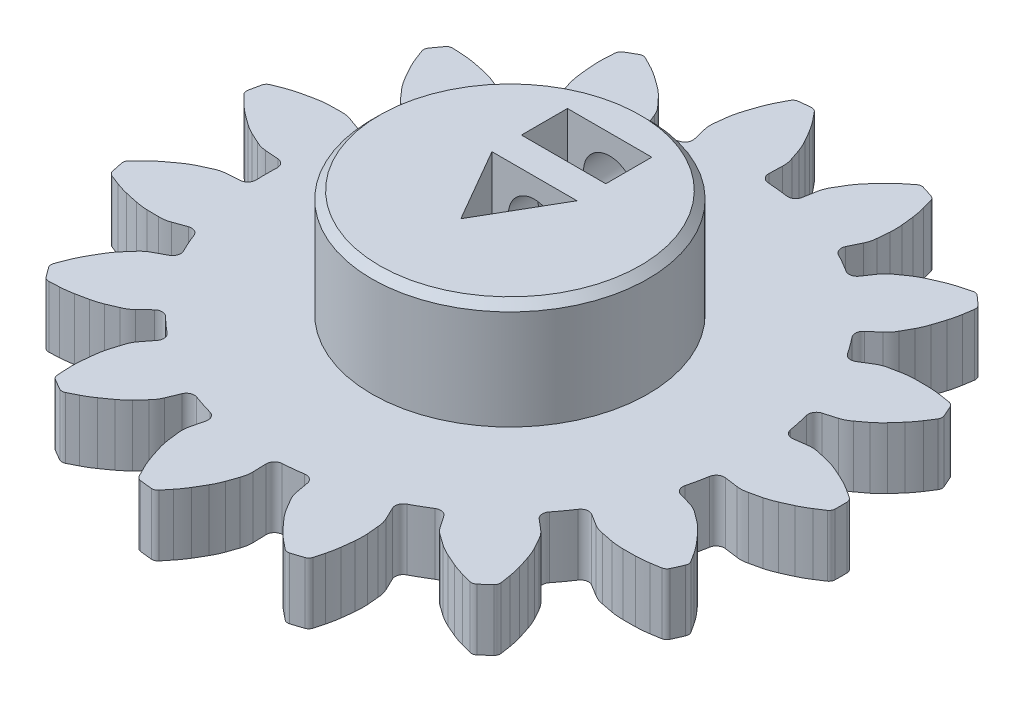
SolidWorks part; units mm, degrees
ref_plane "Front Plane" through (0, 0, 0) normal (0, 0, 1) x (1, 0, 0)
ref_plane "Top Plane" through (0, 0, 0) normal (0, 1, 0) x (1, 0, 0)
ref_plane "Right Plane" through (0, 0, 0) normal (1, 0, 0) x (0, 0, -1)
sketch "Sketch1" plane through (0, 0, 0) normal (0, 1, 0) x (1, 0, 0)
  line L0 (625.6555, 307.002) -> (626.5156, 307.1185)
  line L1 (625.6555, 302.598) -> (626.5156, 302.4815)
  line L2 (625.1464, 300.2026) -> (625.9795, 299.9593)
  line L3 (623.3551, 296.1794) -> (624.0934, 295.7232)
  line L4 (621.9157, 294.1982) -> (622.5778, 293.6371)
  line L5 (618.643, 291.2514) -> (619.1318, 290.5343)
  line L6 (616.5221, 290.027) -> (616.8987, 289.245)
  line L7 (612.3337, 288.6661) -> (612.4887, 287.8121)
  line L8 (609.8982, 288.4101) -> (609.9242, 287.5426)
  line L9 (605.5184, 288.8704) -> (605.3126, 288.0273)
  line L10 (603.1894, 289.6272) -> (602.8603, 288.8241)
  line L11 (599.3755, 291.8292) -> (598.8445, 291.1426)
  line L12 (597.5556, 293.4678) -> (596.9283, 292.868)
  line L13 (594.967, 297.0306) -> (594.2027, 296.6194)
  line L14 (593.9709, 299.2679) -> (593.1539, 298.975)
  line L15 (593.0553, 303.5755) -> (592.1898, 303.5107)
  line L16 (593.0553, 306.0245) -> (592.1898, 306.0893)
  line L17 (593.9709, 310.3321) -> (593.1539, 310.625)
  line L18 (594.967, 312.5694) -> (594.2027, 312.9806)
  line L19 (597.5556, 316.1322) -> (596.9283, 316.732)
  line L20 (599.3755, 317.7708) -> (598.8445, 318.4574)
  line L21 (603.1894, 319.9728) -> (602.8603, 320.7759)
  line L22 (605.5184, 320.7296) -> (605.3126, 321.5727)
  line L23 (609.8982, 321.1899) -> (609.9242, 322.0574)
  line L24 (612.3337, 320.9339) -> (612.4887, 321.7879)
  line L25 (616.5221, 319.573) -> (616.8987, 320.355)
  line L26 (618.643, 318.3486) -> (619.1318, 319.0657)
  line L27 (621.9157, 315.4018) -> (622.5778, 315.9629)
  line L28 (623.3551, 313.4206) -> (624.0934, 313.8768)
  line L29 (625.1464, 309.3974) -> (625.9795, 309.6407)
  line L30 (593.5318, 304.8) -> (630.9968, 304.8) construction
  line L31 (607.15, 326.2717) -> (611.0662, 289.012) construction
  arc A0 (625.0608, 307.4397) -> (624.9349, 308.1006) centre (609.4068, 304.8) ccw
  arc A1 (627.2484, 307.0745) -> (626.5156, 307.1185) centre (626.7704, 305.238) ccw
  arc A2 (627.9948, 306.9048) -> (627.2484, 307.0745) centre (97.3308, -2025.8777) ccw
  arc A3 (628.7466, 306.6443) -> (627.9948, 306.9048) centre (626.7164, 302.0004) ccw
  arc A4 (629.499, 306.3037) -> (628.7466, 306.6443) centre (616.4504, 278.4846) ccw
  arc A5 (630.2476, 305.8885) -> (629.499, 306.3037) centre (626.7956, 300.5468) ccw
  arc A6 (630.8146, 305.5178) -> (630.2476, 305.8885) centre (599.5148, 258.2574) ccw
  arc A7 (630.9968, 304.8) -> (630.9932, 305.1924) centre (609.4068, 304.8) ccw
  arc A8 (630.9932, 305.1924) -> (630.8146, 305.5178) centre (630.5943, 305.1852) ccw
  arc A9 (625.0608, 307.4397) -> (625.6555, 307.002) centre (625.5843, 307.528) ccw
  arc A10 (624.9349, 301.4994) -> (625.0608, 302.1603) centre (609.4068, 304.8) ccw
  arc A11 (626.5156, 302.4815) -> (627.2484, 302.5255) centre (626.7704, 304.362) ccw
  arc A12 (627.2484, 302.5255) -> (627.9948, 302.6952) centre (97.3308, 2635.4777) ccw
  arc A13 (627.9948, 302.6952) -> (628.7466, 302.9557) centre (626.7164, 307.5996) ccw
  arc A14 (628.7466, 302.9557) -> (629.499, 303.2963) centre (616.4504, 331.1154) ccw
  arc A15 (629.499, 303.2963) -> (630.2476, 303.7115) centre (626.7956, 309.0532) ccw
  arc A16 (630.2476, 303.7115) -> (630.8146, 304.0822) centre (599.5148, 351.3426) ccw
  arc A17 (630.9932, 304.4076) -> (630.9968, 304.8) centre (609.4068, 304.8) ccw
  arc A18 (630.8146, 304.0822) -> (630.9932, 304.4076) centre (630.5943, 304.4148) ccw
  arc A19 (625.6555, 302.598) -> (625.0608, 302.1603) centre (625.5843, 302.072) ccw
  arc A20 (624.7811, 300.8445) -> (624.9349, 301.4994) centre (609.4068, 304.8) ccw
  arc A21 (626.631, 299.621) -> (625.9795, 299.9593) centre (625.4473, 298.1377) ccw
  arc A22 (627.2439, 299.1624) -> (626.631, 299.621) centre (-806.37, -1616.1) ccw
  arc A23 (627.8248, 298.6186) -> (627.2439, 299.1624) centre (624.0812, 295.202) ccw
  arc A24 (628.3735, 298.0014) -> (627.8248, 298.6186) centre (605.138, 277.8948) ccw
  arc A25 (628.8885, 297.3177) -> (628.3735, 298.0014) centre (623.5623, 293.8419) ccw
  arc A26 (629.2558, 296.7484) -> (628.8885, 297.3177) centre (581.4394, 266.3046) ccw
  arc A27 (629.1302, 296.0186) -> (629.2866, 296.3785) centre (609.4068, 304.8) ccw
  arc A28 (629.2866, 296.3785) -> (629.2558, 296.7484) centre (628.9192, 296.5341) ccw
  arc A29 (624.7811, 300.8445) -> (625.1464, 300.2026) centre (625.2952, 300.7122) ccw
  arc A30 (622.2499, 295.4689) -> (622.6337, 296.0214) centre (609.4068, 304.8) ccw
  arc A31 (624.0934, 295.7232) -> (624.7808, 295.4653) centre (625.0911, 297.3375) ccw
  arc A32 (624.7808, 295.4653) -> (625.5316, 295.3167) centre (1089.5741, 2642.2601) ccw
  arc A33 (625.5316, 295.3167) -> (626.3245, 295.2489) centre (626.3586, 300.3171) ccw
  arc A34 (626.3245, 295.2489) -> (627.1503, 295.2541) centre (626.5449, 325.9754) ccw
  arc A35 (627.1503, 295.2541) -> (628.0031, 295.3289) centre (627.0222, 301.6128) ccw
  arc A36 (628.0031, 295.3289) -> (628.6718, 295.4369) centre (619.3006, 351.3423) ccw
  arc A37 (628.9674, 295.6615) -> (629.1302, 296.0186) centre (609.4068, 304.8) ccw
  arc A38 (628.6718, 295.4369) -> (628.9674, 295.6615) centre (628.6059, 295.8304) ccw
  arc A39 (623.3551, 296.1794) -> (622.6337, 296.0214) centre (623.0761, 295.7279) ccw
  arc A40 (621.8431, 294.9331) -> (622.2499, 295.4689) centre (609.4068, 304.8) ccw
  arc A41 (623.0354, 293.0631) -> (622.5778, 293.6371) centre (621.3508, 292.1894) ccw
  arc A42 (623.4088, 292.3948) -> (623.0354, 293.0631) centre (-1465.27, -874.1812) ccw
  arc A43 (623.7183, 291.6618) -> (623.4088, 292.3948) centre (618.9087, 290.0631) ccw
  arc A44 (623.9685, 290.8747) -> (623.7183, 291.6618) centre (594.5637, 281.9572) ccw
  arc A45 (624.1609, 290.0406) -> (623.9685, 290.8747) centre (617.8814, 289.0317) ccw
  arc A46 (624.2649, 289.3712) -> (624.1609, 290.0406) centre (568.1998, 281.0081) ccw
  arc A47 (623.8533, 288.7555) -> (624.1426, 289.0207) centre (609.4068, 304.8) ccw
  arc A48 (624.1426, 289.0207) -> (624.2649, 289.3712) centre (623.8702, 289.3123) ccw
  arc A49 (621.8431, 294.9331) -> (621.9157, 294.1982) centre (622.2589, 294.6032) ccw
  arc A50 (617.3443, 291.0518) -> (617.9196, 291.4005) centre (609.4068, 304.8) ccw
  arc A51 (619.1318, 290.5343) -> (619.6548, 290.0192) centre (620.6998, 291.6033) ccw
  arc A52 (619.6548, 290.0192) -> (620.2804, 289.578) centre (1998.7922, 2244.8744) ccw
  arc A53 (620.2804, 289.578) -> (620.9771, 289.1936) centre (623.0697, 293.8098) ccw
  arc A54 (620.9771, 289.1936) -> (621.7337, 288.8624) centre (633.676, 317.174) ccw
  arc A55 (621.7337, 288.8624) -> (622.5431, 288.5839) centre (624.2029, 294.7236) ccw
  arc A56 (622.5431, 288.5839) -> (623.198, 288.4106) centre (637.3756, 343.2943) ccw
  arc A57 (623.5593, 288.4956) -> (623.8533, 288.7555) centre (609.4068, 304.8) ccw
  arc A58 (623.198, 288.4106) -> (623.5593, 288.4956) centre (623.2978, 288.7969) ccw
  arc A59 (618.643, 291.2514) -> (617.9196, 291.4005) centre (618.2043, 290.9524) ccw
  arc A60 (616.7547, 290.7279) -> (617.3443, 291.0518) centre (609.4068, 304.8) ccw
  arc A61 (617.0833, 288.5345) -> (616.8987, 289.245) centre (615.189, 288.4216) ccw
  arc A62 (617.1526, 287.7722) -> (617.0833, 288.5345) centre (-1765.4397, 71.5942) ccw
  arc A63 (617.1372, 286.9766) -> (617.1526, 287.7722) centre (612.0932, 287.4725) ccw
  arc A64 (617.0457, 286.1558) -> (617.1372, 286.9766) centre (586.556, 289.9693) ccw
  arc A65 (616.8822, 285.3156) -> (617.0457, 286.1558) centre (610.7352, 286.948) ccw
  arc A66 (616.7049, 284.6618) -> (616.8822, 285.3156) centre (562.0853, 299.8254) ccw
  arc A67 (616.0785, 284.2667) -> (616.4506, 284.3913) centre (609.4068, 304.8) ccw
  arc A68 (616.4506, 284.3913) -> (616.7049, 284.6618) centre (616.3204, 284.7685) ccw
  arc A69 (616.7547, 290.7279) -> (616.5221, 290.027) centre (617.0004, 290.2573) ccw
  arc A70 (611.0662, 289.012) -> (611.7336, 289.0964) centre (609.4068, 304.8) ccw
  arc A71 (612.4887, 287.8121) -> (612.757, 287.1288) centre (614.3559, 288.1509) ccw
  arc A72 (612.757, 287.1288) -> (613.149, 286.4713) centre (2667.7729, 1512.0322) ccw
  arc A73 (613.149, 286.4713) -> (613.6291, 285.8368) centre (617.4184, 289.2027) ccw
  arc A74 (613.6291, 285.8368) -> (614.1855, 285.2265) centre (636.6108, 306.2331) ccw
  arc A75 (614.1855, 285.2265) -> (614.8117, 284.6429) centre (618.8253, 289.5766) ccw
  arc A76 (614.8117, 284.6429) -> (615.3395, 284.2181) centre (650.6147, 328.5903) ccw
  arc A77 (615.7042, 284.1488) -> (616.0785, 284.2667) centre (609.4068, 304.8) ccw
  arc A78 (615.3395, 284.2181) -> (615.7042, 284.1488) centre (615.5878, 284.5305) ccw
  arc A79 (612.3337, 288.6661) -> (611.7336, 289.0964) centre (611.8114, 288.5713) ccw
  arc A80 (610.3958, 288.9558) -> (611.0662, 289.012) centre (609.4068, 304.8) ccw
  arc A81 (609.8039, 286.8184) -> (609.9242, 287.5426) centre (608.0274, 287.4858) ccw
  arc A82 (609.5571, 286.0938) -> (609.8039, 286.8184) centre (-1654.9767, 1057.693) ccw
  arc A83 (609.2194, 285.3733) -> (609.5571, 286.0938) centre (604.8132, 287.8779) ccw
  arc A84 (608.802, 284.6607) -> (609.2194, 285.3733) centre (582.4993, 300.5457) ccw
  arc A85 (608.3109, 283.9596) -> (608.802, 284.6607) centre (603.3593, 287.951) ccw
  arc A86 (607.8829, 283.4344) -> (608.3109, 283.9596) centre (564.1531, 319.5029) ccw
  arc A87 (607.15, 283.3283) -> (607.5407, 283.2908) centre (609.4068, 304.8) ccw
  arc A88 (607.5407, 283.2908) -> (607.8829, 283.4344) centre (607.5752, 283.6883) ccw
  arc A89 (610.3958, 288.9558) -> (609.8982, 288.4101) centre (610.4289, 288.426) ccw
  arc A90 (604.5011, 289.702) -> (605.1452, 289.5077) centre (609.4068, 304.8) ccw
  arc A91 (605.3126, 288.0273) -> (605.2798, 287.2939) centre (607.1562, 287.5773) ccw
  arc A92 (605.2798, 287.2939) -> (605.3705, 286.5339) centre (2980.8434, 570.4486) ccw
  arc A93 (605.3705, 286.5339) -> (605.551, 285.7589) centre (610.3817, 287.2926) ccw
  arc A94 (605.551, 285.7589) -> (605.8111, 284.975) centre (634.8418, 295.0443) ccw
  arc A95 (605.8111, 284.975) -> (606.1458, 284.1872) centre (611.8191, 287.0619) ccw
  arc A96 (606.1458, 284.1872) -> (606.4552, 283.5845) centre (656.7285, 309.7728) ccw
  arc A97 (606.7601, 283.3728) -> (607.15, 283.3283) centre (609.4068, 304.8) ccw
  arc A98 (606.4552, 283.5845) -> (606.7601, 283.3728) centre (606.809, 283.7688) ccw
  arc A99 (605.5184, 288.8704) -> (605.1452, 289.5077) centre (605.0027, 288.9963) ccw
  arc A100 (603.8659, 289.9234) -> (604.5011, 289.702) centre (609.4068, 304.8) ccw
  arc A101 (602.4558, 288.2115) -> (602.8603, 288.8241) centre (601.1043, 289.5437) ccw
  arc A102 (601.9356, 287.6499) -> (602.4558, 288.2115) centre (-1152.9813, 1913.6097) ccw
  arc A103 (601.3341, 287.1291) -> (601.9356, 287.6499) centre (598.3274, 291.2093) ccw
  arc A104 (600.6629, 286.6478) -> (601.3341, 287.1291) centre (583.0952, 311.8578) ccw
  arc A105 (599.9291, 286.2071) -> (600.6629, 286.6478) centre (597.029, 291.8675) ccw
  arc A106 (599.3245, 285.9014) -> (599.9291, 286.2071) centre (574.0457, 336.6381) ccw
  arc A107 (598.6118, 286.1025) -> (598.9534, 285.9094) centre (609.4068, 304.8) ccw
  arc A108 (598.9534, 285.9094) -> (599.3245, 285.9014) centre (599.1466, 286.2585) ccw
  arc A109 (603.8659, 289.9234) -> (603.1894, 289.6272) centre (603.6806, 289.4259) ccw
  arc A110 (598.7843, 293.0026) -> (599.2937, 292.5631) centre (609.4068, 304.8) ccw
  arc A111 (598.8445, 291.1426) -> (598.5162, 290.486) centre (600.3457, 289.9817) ccw
  arc A112 (598.5162, 290.486) -> (598.29, 289.7548) centre (2883.8709, -417.068) ccw
  arc A113 (598.29, 289.7548) -> (598.1397, 288.9734) centre (603.1765, 288.4096) ccw
  arc A114 (598.1397, 288.9734) -> (598.0585, 288.1515) centre (628.6748, 285.5424) ccw
  arc A115 (598.0585, 288.1515) -> (598.0437, 287.2956) centre (604.3958, 287.6143) ccw
  arc A116 (598.0437, 287.2956) -> (598.0812, 286.6192) centre (654.6599, 290.0954) ccw
  arc A117 (598.2737, 286.3018) -> (598.6118, 286.1025) centre (609.4068, 304.8) ccw
  arc A118 (598.0812, 286.6192) -> (598.2737, 286.3018) centre (598.4795, 286.6437) ccw
  arc A119 (599.3755, 291.8292) -> (599.2937, 292.5631) centre (598.9555, 292.1539) ccw
  arc A120 (598.294, 293.4632) -> (598.7843, 293.0026) centre (609.4068, 304.8) ccw
  arc A121 (596.3096, 292.4729) -> (596.9283, 292.868) centre (595.6168, 294.2396) ccw
  arc A122 (595.606, 292.1714) -> (596.3096, 292.4729) centre (-346.253, 2491.3486) ccw
  arc A123 (594.8446, 291.9402) -> (595.606, 292.1714) centre (593.7574, 296.8906) ccw
  arc A124 (594.0357, 291.7736) -> (594.8446, 291.9402) centre (588.2406, 321.9495) ccw
  arc A125 (593.186, 291.6695) -> (594.0357, 291.7736) centre (592.839, 298.02) ccw
  arc A126 (592.5094, 291.6361) -> (593.186, 291.6695) centre (590.0525, 348.2682) ccw
  arc A127 (591.9401, 292.1097) -> (592.1737, 291.7943) centre (609.4068, 304.8) ccw
  arc A128 (592.1737, 291.7943) -> (592.5094, 291.6361) centre (592.4921, 292.0347) ccw
  arc A129 (598.294, 293.4632) -> (597.5556, 293.4678) centre (597.9224, 293.0841) ccw
  arc A130 (594.9043, 298.3431) -> (595.1908, 297.7344) centre (609.4068, 304.8) ccw
  arc A131 (594.2027, 296.6194) -> (593.6357, 296.1531) centre (595.1019, 294.9483) ccw
  arc A132 (593.6357, 296.1531) -> (593.1316, 295.5771) centre (2393.623, -1279.7672) ccw
  arc A133 (593.1316, 295.5771) -> (592.6765, 294.9244) centre (597.0486, 292.3607) ccw
  arc A134 (592.6765, 294.9244) -> (592.268, 294.2066) centre (619.1762, 279.3703) ccw
  arc A135 (592.268, 294.2066) -> (591.9064, 293.4307) centre (597.8389, 291.1382) ccw
  arc A136 (591.9064, 293.4307) -> (591.6656, 292.7975) centre (644.7667, 272.9606) ccw
  arc A137 (591.7123, 292.4293) -> (591.9401, 292.1097) centre (609.4068, 304.8) ccw
  arc A138 (591.6656, 292.7975) -> (591.7123, 292.4293) centre (592.0393, 292.6579) ccw
  arc A139 (594.967, 297.0306) -> (595.1908, 297.7344) centre (594.7155, 297.4981) ccw
  arc A140 (594.6437, 298.9633) -> (594.9043, 298.3431) centre (609.4068, 304.8) ccw
  arc A141 (592.428, 298.8657) -> (593.1539, 298.975) centre (592.5137, 300.7615) ccw
  arc A142 (591.6626, 298.8765) -> (592.428, 298.8657) centre (625.7176, 2691.0134) ccw
  arc A143 (590.873, 298.975) -> (591.6626, 298.8765) centre (591.8934, 303.9396) ccw
  arc A144 (590.0663, 299.1518) -> (590.873, 298.975) centre (597.0459, 329.0759) ccw
  arc A145 (589.2477, 299.4022) -> (590.0663, 299.1518) centre (591.5137, 305.3449) ccw
  arc A146 (588.616, 299.6469) -> (589.2477, 299.4022) centre (609.4059, 352.3822) ccw
  arc A147 (588.2886, 300.3112) -> (588.3737, 299.9281) centre (609.4068, 304.8) ccw
  arc A148 (588.3737, 299.9281) -> (588.616, 299.6469) centre (588.7624, 300.0181) ccw
  arc A149 (594.6437, 298.9633) -> (593.9709, 299.2679) centre (594.15, 298.7681) ccw
  arc A150 (593.5318, 304.8) -> (593.546, 304.1274) centre (609.4068, 304.8) ccw
  arc A151 (592.1898, 303.5107) -> (591.4822, 303.3153) centre (592.3316, 301.6183) ccw
  arc A152 (591.4822, 303.3153) -> (590.7874, 302.9942) centre (1594.8679, -1868.4803) ccw
  arc A153 (590.7874, 302.9942) -> (590.1061, 302.583) centre (593.0575, 298.4627) ccw
  arc A154 (590.1061, 302.583) -> (589.441, 302.0934) centre (607.9884, 277.5952) ccw
  arc A155 (589.441, 302.0934) -> (588.7951, 301.5317) centre (593.2823, 297.0244) ccw
  arc A156 (588.7951, 301.5317) -> (588.3175, 301.0512) centre (628.7594, 261.3311) ccw
  arc A157 (588.2105, 300.6958) -> (588.2886, 300.3112) centre (609.4068, 304.8) ccw
  arc A158 (588.3175, 301.0512) -> (588.2105, 300.6958) centre (588.6022, 300.7716) ccw
  arc A159 (593.0553, 303.5755) -> (593.546, 304.1274) centre (593.0157, 304.1049) ccw
  arc A160 (593.546, 305.4726) -> (593.5318, 304.8) centre (609.4068, 304.8) ccw
  arc A161 (591.4822, 306.2847) -> (592.1898, 306.0893) centre (592.3316, 307.9817) ccw
  arc A162 (590.7874, 306.6058) -> (591.4822, 306.2847) centre (1594.8679, 2478.0803) ccw
  arc A163 (590.1061, 307.017) -> (590.7874, 306.6058) centre (593.0575, 311.1373) ccw
  arc A164 (589.441, 307.5066) -> (590.1061, 307.017) centre (607.9884, 332.0048) ccw
  arc A165 (588.7951, 308.0683) -> (589.441, 307.5066) centre (593.2823, 312.5756) ccw
  arc A166 (588.3175, 308.5488) -> (588.7951, 308.0683) centre (628.7594, 348.2689) ccw
  arc A167 (588.2886, 309.2888) -> (588.2105, 308.9042) centre (609.4068, 304.8) ccw
  arc A168 (588.2105, 308.9042) -> (588.3175, 308.5488) centre (588.6022, 308.8284) ccw
  arc A169 (593.546, 305.4726) -> (593.0553, 306.0245) centre (593.0157, 305.4951) ccw
  arc A170 (594.9043, 311.2569) -> (594.6437, 310.6367) centre (609.4068, 304.8) ccw
  arc A171 (593.1539, 310.625) -> (592.428, 310.7343) centre (592.5137, 308.8385) ccw
  arc A172 (592.428, 310.7343) -> (591.6626, 310.7235) centre (625.7176, -2081.4134) ccw
  arc A173 (591.6626, 310.7235) -> (590.873, 310.625) centre (591.8934, 305.6604) ccw
  arc A174 (590.873, 310.625) -> (590.0663, 310.4482) centre (597.0459, 280.5241) ccw
  arc A175 (590.0663, 310.4482) -> (589.2477, 310.1978) centre (591.5137, 304.2551) ccw
  arc A176 (589.2477, 310.1978) -> (588.616, 309.9531) centre (609.4059, 257.2178) ccw
  arc A177 (588.3737, 309.6719) -> (588.2886, 309.2888) centre (609.4068, 304.8) ccw
  arc A178 (588.616, 309.9531) -> (588.3737, 309.6719) centre (588.7624, 309.5819) ccw
  arc A179 (593.9709, 310.3321) -> (594.6437, 310.6367) centre (594.15, 310.8319) ccw
  arc A180 (595.1908, 311.8656) -> (594.9043, 311.2569) centre (609.4068, 304.8) ccw
  arc A181 (593.6357, 313.4469) -> (594.2027, 312.9806) centre (595.1019, 314.6517) ccw
  arc A182 (593.1316, 314.0229) -> (593.6357, 313.4469) centre (2393.623, 1889.3672) ccw
  arc A183 (592.6765, 314.6756) -> (593.1316, 314.0229) centre (597.0486, 317.2393) ccw
  arc A184 (592.268, 315.3934) -> (592.6765, 314.6756) centre (619.1762, 330.2297) ccw
  arc A185 (591.9064, 316.1693) -> (592.268, 315.3934) centre (597.8389, 318.4618) ccw
  arc A186 (591.6656, 316.8025) -> (591.9064, 316.1693) centre (644.7667, 336.6394) ccw
  arc A187 (591.9401, 317.4903) -> (591.7123, 317.1707) centre (609.4068, 304.8) ccw
  arc A188 (591.7123, 317.1707) -> (591.6656, 316.8025) centre (592.0393, 316.9421) ccw
  arc A189 (595.1908, 311.8656) -> (594.967, 312.5694) centre (594.7155, 312.1019) ccw
  arc A190 (598.7843, 316.5974) -> (598.294, 316.1368) centre (609.4068, 304.8) ccw
  arc A191 (596.9283, 316.732) -> (596.3096, 317.1271) centre (595.6168, 315.3604) ccw
  arc A192 (596.3096, 317.1271) -> (595.606, 317.4286) centre (-346.253, -1881.7486) ccw
  arc A193 (595.606, 317.4286) -> (594.8446, 317.6598) centre (593.7574, 312.7094) ccw
  arc A194 (594.8446, 317.6598) -> (594.0357, 317.8264) centre (588.2406, 287.6505) ccw
  arc A195 (594.0357, 317.8264) -> (593.186, 317.9305) centre (592.839, 311.58) ccw
  arc A196 (593.186, 317.9305) -> (592.5094, 317.9639) centre (590.0525, 261.3318) ccw
  arc A197 (592.1737, 317.8057) -> (591.9401, 317.4903) centre (609.4068, 304.8) ccw
  arc A198 (592.5094, 317.9639) -> (592.1737, 317.8057) centre (592.4921, 317.5653) ccw
  arc A199 (597.5556, 316.1322) -> (598.294, 316.1368) centre (597.9224, 316.5159) ccw
  arc A200 (599.2937, 317.0369) -> (598.7843, 316.5974) centre (609.4068, 304.8) ccw
  arc A201 (598.5162, 319.114) -> (598.8445, 318.4574) centre (600.3457, 319.6183) ccw
  arc A202 (598.29, 319.8452) -> (598.5162, 319.114) centre (2883.8709, 1026.668) ccw
  arc A203 (598.1397, 320.6266) -> (598.29, 319.8452) centre (603.1765, 321.1904) ccw
  arc A204 (598.0585, 321.4485) -> (598.1397, 320.6266) centre (628.6748, 324.0576) ccw
  arc A205 (598.0437, 322.3044) -> (598.0585, 321.4485) centre (604.3958, 321.9857) ccw
  arc A206 (598.0812, 322.9808) -> (598.0437, 322.3044) centre (654.6599, 319.5046) ccw
  arc A207 (598.6118, 323.4975) -> (598.2737, 323.2982) centre (609.4068, 304.8) ccw
  arc A208 (598.2737, 323.2982) -> (598.0812, 322.9808) centre (598.4795, 322.9563) ccw
  arc A209 (599.2937, 317.0369) -> (599.3755, 317.7708) centre (598.9555, 317.4461) ccw
  arc A210 (604.5011, 319.898) -> (603.8659, 319.6766) centre (609.4068, 304.8) ccw
  arc A211 (602.8603, 320.7759) -> (602.4558, 321.3885) centre (601.1043, 320.0563) ccw
  arc A212 (602.4558, 321.3885) -> (601.9356, 321.9501) centre (-1152.9813, -1304.0097) ccw
  arc A213 (601.9356, 321.9501) -> (601.3341, 322.4709) centre (598.3274, 318.3907) ccw
  arc A214 (601.3341, 322.4709) -> (600.6629, 322.9522) centre (583.0952, 297.7422) ccw
  arc A215 (600.6629, 322.9522) -> (599.9291, 323.3929) centre (597.029, 317.7325) ccw
  arc A216 (599.9291, 323.3929) -> (599.3245, 323.6986) centre (574.0457, 272.9619) ccw
  arc A217 (598.9534, 323.6906) -> (598.6118, 323.4975) centre (609.4068, 304.8) ccw
  arc A218 (599.3245, 323.6986) -> (598.9534, 323.6906) centre (599.1466, 323.3415) ccw
  arc A219 (603.1894, 319.9728) -> (603.8659, 319.6766) centre (603.6806, 320.1741) ccw
  arc A220 (605.1452, 320.0923) -> (604.5011, 319.898) centre (609.4068, 304.8) ccw
  arc A221 (605.2798, 322.3061) -> (605.3126, 321.5727) centre (607.1562, 322.0227) ccw
  arc A222 (605.3705, 323.0661) -> (605.2798, 322.3061) centre (2980.8434, 39.1514) ccw
  arc A223 (605.551, 323.8411) -> (605.3705, 323.0661) centre (610.3817, 322.3074) ccw
  arc A224 (605.8111, 324.625) -> (605.551, 323.8411) centre (634.8418, 314.5557) ccw
  arc A225 (606.1458, 325.4128) -> (605.8111, 324.625) centre (611.8191, 322.5381) ccw
  arc A226 (606.4552, 326.0155) -> (606.1458, 325.4128) centre (656.7285, 299.8272) ccw
  arc A227 (607.15, 326.2717) -> (606.7601, 326.2272) centre (609.4068, 304.8) ccw
  arc A228 (606.7601, 326.2272) -> (606.4552, 326.0155) centre (606.809, 325.8312) ccw
  arc A229 (605.1452, 320.0923) -> (605.5184, 320.7296) centre (605.0027, 320.6037) ccw
  arc A230 (611.0662, 320.588) -> (610.3958, 320.6442) centre (609.4068, 304.8) ccw
  arc A231 (609.9242, 322.0574) -> (609.8039, 322.7816) centre (608.0274, 322.1142) ccw
  arc A232 (609.8039, 322.7816) -> (609.5571, 323.5062) centre (-1654.9767, -448.093) ccw
  arc A233 (609.5571, 323.5062) -> (609.2194, 324.2267) centre (604.8132, 321.7221) ccw
  arc A234 (609.2194, 324.2267) -> (608.802, 324.9393) centre (582.4993, 309.0543) ccw
  arc A235 (608.802, 324.9393) -> (608.3109, 325.6404) centre (603.3593, 321.649) ccw
  arc A236 (608.3109, 325.6404) -> (607.8829, 326.1656) centre (564.1531, 290.0971) ccw
  arc A237 (607.5407, 326.3092) -> (607.15, 326.2717) centre (609.4068, 304.8) ccw
  arc A238 (607.8829, 326.1656) -> (607.5407, 326.3092) centre (607.5752, 325.9117) ccw
  arc A239 (609.8982, 321.1899) -> (610.3958, 320.6442) centre (610.4289, 321.174) ccw
  arc A240 (611.7336, 320.5036) -> (611.0662, 320.588) centre (609.4068, 304.8) ccw
  arc A241 (612.757, 322.4712) -> (612.4887, 321.7879) centre (614.3559, 321.4491) ccw
  arc A242 (613.149, 323.1287) -> (612.757, 322.4712) centre (2667.7729, -902.4322) ccw
  arc A243 (613.6291, 323.7632) -> (613.149, 323.1287) centre (617.4184, 320.3973) ccw
  arc A244 (614.1855, 324.3735) -> (613.6291, 323.7632) centre (636.6108, 303.3669) ccw
  arc A245 (614.8117, 324.9571) -> (614.1855, 324.3735) centre (618.8253, 320.0234) ccw
  arc A246 (615.3395, 325.3819) -> (614.8117, 324.9571) centre (650.6147, 281.0097) ccw
  arc A247 (616.0785, 325.3333) -> (615.7042, 325.4512) centre (609.4068, 304.8) ccw
  arc A248 (615.7042, 325.4512) -> (615.3395, 325.3819) centre (615.5878, 325.0695) ccw
  arc A249 (611.7336, 320.5036) -> (612.3337, 320.9339) centre (611.8114, 321.0287) ccw
  arc A250 (617.3443, 318.5482) -> (616.7547, 318.8721) centre (609.4068, 304.8) ccw
  arc A251 (616.8987, 320.355) -> (617.0833, 321.0655) centre (615.189, 321.1784) ccw
  arc A252 (617.0833, 321.0655) -> (617.1526, 321.8278) centre (-1765.4397, 538.0058) ccw
  arc A253 (617.1526, 321.8278) -> (617.1372, 322.6234) centre (612.0932, 322.1275) ccw
  arc A254 (617.1372, 322.6234) -> (617.0457, 323.4442) centre (586.556, 319.6307) ccw
  arc A255 (617.0457, 323.4442) -> (616.8822, 324.2844) centre (610.7352, 322.652) ccw
  arc A256 (616.8822, 324.2844) -> (616.7049, 324.9382) centre (562.0853, 309.7746) ccw
  arc A257 (616.4506, 325.2087) -> (616.0785, 325.3333) centre (609.4068, 304.8) ccw
  arc A258 (616.7049, 324.9382) -> (616.4506, 325.2087) centre (616.3204, 324.8315) ccw
  arc A259 (616.5221, 319.573) -> (616.7547, 318.8721) centre (617.0004, 319.3427) ccw
  arc A260 (617.9196, 318.1995) -> (617.3443, 318.5482) centre (609.4068, 304.8) ccw
  arc A261 (619.6548, 319.5808) -> (619.1318, 319.0657) centre (620.6998, 317.9967) ccw
  arc A262 (620.2804, 320.022) -> (619.6548, 319.5808) centre (1998.7922, -1635.2744) ccw
  arc A263 (620.9771, 320.4064) -> (620.2804, 320.022) centre (623.0697, 315.7902) ccw
  arc A264 (621.7337, 320.7376) -> (620.9771, 320.4064) centre (633.676, 292.426) ccw
  arc A265 (622.5431, 321.0161) -> (621.7337, 320.7376) centre (624.2029, 314.8764) ccw
  arc A266 (623.198, 321.1894) -> (622.5431, 321.0161) centre (637.3756, 266.3057) ccw
  arc A267 (623.8533, 320.8445) -> (623.5593, 321.1044) centre (609.4068, 304.8) ccw
  arc A268 (623.5593, 321.1044) -> (623.198, 321.1894) centre (623.2978, 320.8031) ccw
  arc A269 (617.9196, 318.1995) -> (618.643, 318.3486) centre (618.2043, 318.6476) ccw
  arc A270 (622.2499, 314.1311) -> (621.8431, 314.6669) centre (609.4068, 304.8) ccw
  arc A271 (622.5778, 315.9629) -> (623.0354, 316.5369) centre (621.3508, 317.4106) ccw
  arc A272 (623.0354, 316.5369) -> (623.4088, 317.2052) centre (-1465.27, 1483.7812) ccw
  arc A273 (623.4088, 317.2052) -> (623.7183, 317.9382) centre (618.9087, 319.5369) ccw
  arc A274 (623.7183, 317.9382) -> (623.9685, 318.7253) centre (594.5637, 327.6428) ccw
  arc A275 (623.9685, 318.7253) -> (624.1609, 319.5594) centre (617.8814, 320.5683) ccw
  arc A276 (624.1609, 319.5594) -> (624.2649, 320.2288) centre (568.1998, 328.5919) ccw
  arc A277 (624.1426, 320.5793) -> (623.8533, 320.8445) centre (609.4068, 304.8) ccw
  arc A278 (624.2649, 320.2288) -> (624.1426, 320.5793) centre (623.8702, 320.2877) ccw
  arc A279 (621.9157, 315.4018) -> (621.8431, 314.6669) centre (622.2589, 314.9968) ccw
  arc A280 (622.6337, 313.5786) -> (622.2499, 314.1311) centre (609.4068, 304.8) ccw
  arc A281 (624.7808, 314.1347) -> (624.0934, 313.8768) centre (625.0911, 312.2625) ccw
  arc A282 (625.5316, 314.2833) -> (624.7808, 314.1347) centre (1089.5741, -2032.6601) ccw
  arc A283 (626.3245, 314.3511) -> (625.5316, 314.2833) centre (626.3586, 309.2829) ccw
  arc A284 (627.1503, 314.3459) -> (626.3245, 314.3511) centre (626.5449, 283.6246) ccw
  arc A285 (628.0031, 314.2711) -> (627.1503, 314.3459) centre (627.0222, 307.9872) ccw
  arc A286 (628.6718, 314.1631) -> (628.0031, 314.2711) centre (619.3006, 258.2577) ccw
  arc A287 (629.1302, 313.5814) -> (628.9674, 313.9385) centre (609.4068, 304.8) ccw
  arc A288 (628.9674, 313.9385) -> (628.6718, 314.1631) centre (628.6059, 313.7696) ccw
  arc A289 (622.6337, 313.5786) -> (623.3551, 313.4206) centre (623.0761, 313.8721) ccw
  arc A290 (624.9349, 308.1006) -> (624.7811, 308.7555) centre (609.4068, 304.8) ccw
  arc A291 (625.9795, 309.6407) -> (626.631, 309.979) centre (625.4473, 311.4623) ccw
  arc A292 (626.631, 309.979) -> (627.2439, 310.4376) centre (-806.37, 2225.7) ccw
  arc A293 (627.2439, 310.4376) -> (627.8248, 310.9814) centre (624.0812, 314.398) ccw
  arc A294 (627.8248, 310.9814) -> (628.3735, 311.5986) centre (605.138, 331.7052) ccw
  arc A295 (628.3735, 311.5986) -> (628.8885, 312.2823) centre (623.5623, 315.7581) ccw
  arc A296 (628.8885, 312.2823) -> (629.2558, 312.8516) centre (581.4394, 343.2954) ccw
  arc A297 (629.2866, 313.2215) -> (629.1302, 313.5814) centre (609.4068, 304.8) ccw
  arc A298 (629.2558, 312.8516) -> (629.2866, 313.2215) centre (628.9192, 313.0659) ccw
  arc A299 (625.1464, 309.3974) -> (624.7811, 308.7555) centre (625.2952, 308.8878) ccw
sketch "Sketch2" plane through (0, 0, 0) normal (0, 1, 0) x (1, 0, 0)
  circle A0 centre (609.4068, 304.8) radius 9
  dimension "D1" = 18
sketch "Sketch3" plane through (0, 0, 0) normal (0, 1, 0) x (1, 0, 0)
  line L1 (612.1781, 306.4) -> (606.6355, 306.4)
  line L2 (606.6355, 306.4) -> (609.4068, 301.6)
  line L3 (609.4068, 301.6) -> (612.1781, 306.4)
  circle A0 centre (609.4068, 304.8) radius 1.6 construction
  dimension "D1" = 3.2
extrude "Boss-Extrude1" add sketch "Sketch1" along normal blind 4
extrude "Boss-Extrude2" add sketch "Sketch2" along normal blind 11
extrude "Cut-Extrude1" cut sketch "Sketch3" along normal through all
sketch "Sketch4" plane through (0, 11, 0) normal (0, 1, 0) x (1, 0, 0)
  line L0 (612.1781, 306.4) -> (606.6355, 306.4) construction
  line L1 (606.6568, 311.3) -> (612.1568, 311.3)
  line L2 (606.6568, 311.3) -> (606.6568, 308.3)
  line L3 (606.6568, 308.3) -> (612.1568, 308.3)
  line L4 (612.1568, 311.3) -> (612.1568, 308.3)
  line L5 (606.6568, 311.3) -> (612.1568, 308.3) construction
  line L6 (606.6568, 308.3) -> (612.1568, 311.3) construction
  circle A0 centre (609.4068, 304.8) radius 9 construction
  point P0 (609.4068, 309.8)
  point P7 (609.4068, 306.4)
  point P8 (609.4068, 304.8)
  dimension "D1" = 5
  dimension "D2" = 5.5
  dimension "D3" = 3
extrude "Cut-Extrude2" cut sketch "Sketch4" against normal blind 6
sketch "Sketch5" plane through (0, 0, -306.4) normal (0, 0, 1) x (1, 0, 0)
  line L0 (612.1781, 11) -> (606.6355, 11) construction
  circle A0 centre (609.4068, 8) radius 1.7
  point P4 (609.4068, 11)
  dimension "D2" = 3.4
  dimension "D1" = 3
extrude "Cut-Extrude3" cut sketch "Sketch5" against normal through all
chamfer "Chamfer1" distance 0.5 angle 45 1 edges at (609.4068, 11, -295.8)
